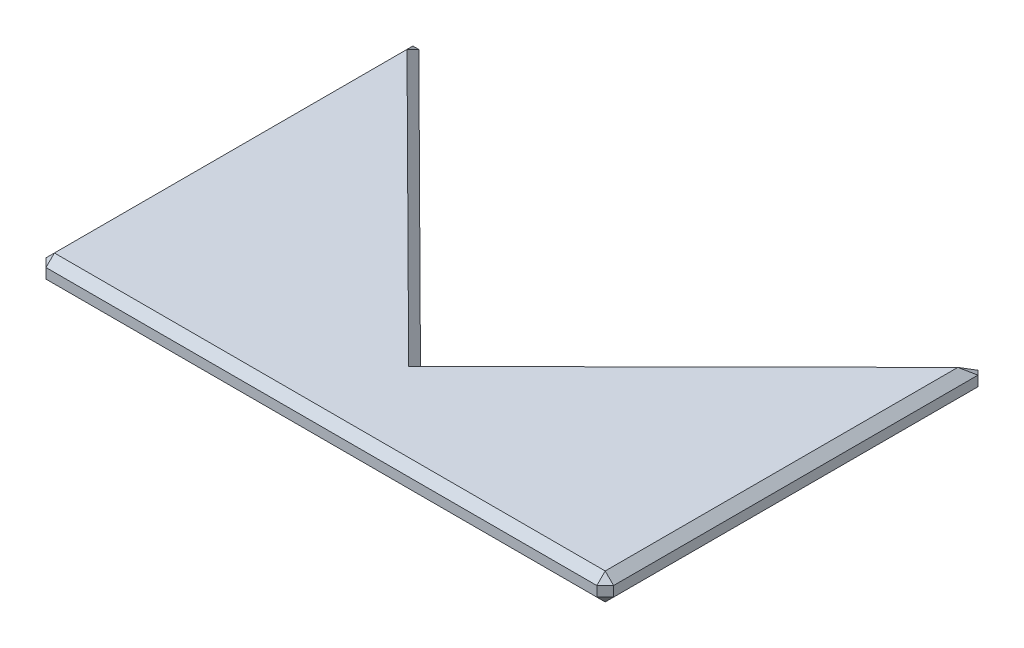
SolidWorks part; units mm, degrees
ref_plane "Front Plane" through (0, 0, 0) normal (0, 0, 1) x (1, 0, 0)
ref_plane "Top Plane" through (0, 0, 0) normal (0, 1, 0) x (1, 0, 0)
ref_plane "Right Plane" through (0, 0, 0) normal (1, 0, 0) x (0, 0, -1)
sketch "Sketch1" plane through (0, 0, 0) normal (0, 1, 0) x (1, 0, 0)
  line L0 (16.9, 22.7) -> (16.9, 0)
  line L1 (16.9, 0) -> (-16.9, 0)
  line L2 (-16.9, 0) -> (-16.9, 22.7)
  line L3 (-16.9, 22.7) -> (0, 5.9)
  line L4 (0, 5.9) -> (16.9, 22.7)
  point P4 (0, 0)
  point P11 (0, 29.3886)
  point P12 (-1.4146, 29.9506)
  point P14 (0, 0)
  dimension "D1" = 22.7
  dimension "D2" = 16.9
  dimension "D3" = 5.9
  dimension "D4" = 33.8
  dimension "D5" = 22.7
extrude "Boss-Extrude1" add sketch "Sketch1" along normal blind 1.6
chamfer "Chamfer1" distance 0.5 angle 45 14 edges at (-16.9, 0.8, -22.7) (16.9, 0.8, -22.7) (0, 0, 0) (16.9, 0.8, 0) (0, 1.6, 0) (16.9, 0, -11.35) (8.45, 0, -14.3) (-8.45, 0, -14.3) (-16.9, 0, -11.35) (-16.9, 0.8, 0) (-16.9, 1.6, -11.35) (-8.45, 1.6, -14.3) (8.45, 1.6, -14.3) (16.9, 1.6, -11.35)
